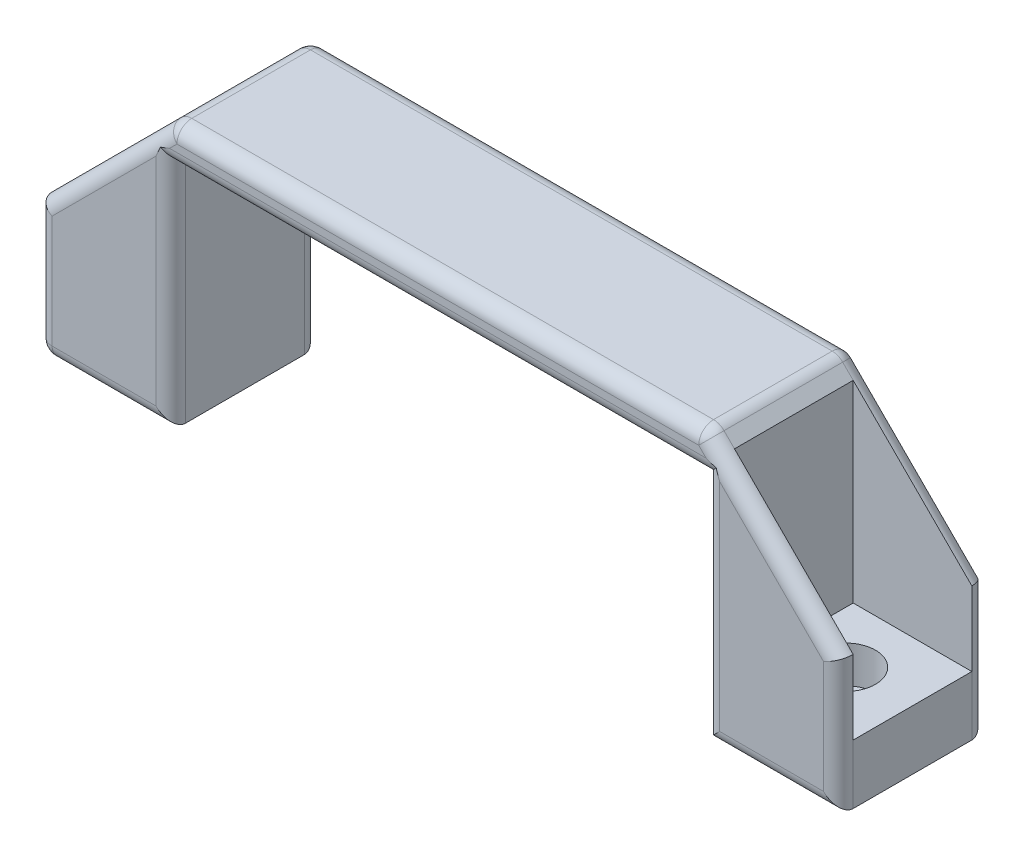
SolidWorks part; units mm, degrees
ref_plane "前视基准面" through (0, 0, 0) normal (0, 0, 1) x (1, 0, 0)
ref_plane "上视基准面" through (0, 0, 0) normal (0, 1, 0) x (1, 0, 0)
ref_plane "右视基准面" through (0, 0, 0) normal (1, 0, 0) x (0, 0, -1)
other "Configuration Table"
sketch "草图1" plane through (0, 0, 0) normal (0, 0, 1) x (1, 0, 0)
  line L0 (-54, 0) -> (-54, 18)
  line L1 (-36, 36) -> (-54, 18)
  line L2 (-36, 0) -> (-36, 31)
  line L3 (-36, 36) -> (36, 36)
  line L4 (-54, 0) -> (-36, 0)
  line L5 (54, 0) -> (36, 0)
  line L6 (-36, 31) -> (36, 31)
  line L7 (0, 31) -> (0, 0) construction
  line L8 (36, 0) -> (36, 31)
  line L9 (36, 36) -> (54, 18)
  line L10 (54, 0) -> (54, 18)
  point P2 (-37.8136, 30)
  point P3 (-54, 18.7225)
  point P8 (-41.4613, 36)
  point P16 (0, 36)
  dimension "D1" = 31
  dimension "D2" = 5
  dimension "D3" = 18
  dimension "D4" = 108
  dimension "D5" = 18
  dimension "D6" = 135
extrude "凸台-拉伸1" add sketch "草图1" along normal mid plane 20
sketch "草图2" plane through (0, 0, 0) normal (0, 1, 0) x (1, 0, 0)
  line L0 (0, 0) -> (0, 23.9133) construction
  circle A0 centre (-45, 0) radius 2.15
  circle A1 centre (45, 0) radius 2.15
  point P7 (0, 0)
  dimension "D1" = 90
  dimension "D2" = 4.3
extrude "切除-拉伸1" cut sketch "草图2" along normal through all
sketch "草图3" plane through (0, 0, 0) normal (0, -1, 0) x (1, 0, 0)
  line L4 (-54, 10) -> (-54, -10) construction
  line L5 (-54, 8) -> (-54, -8)
  line L6 (0, 0) -> (0, 32.7888) construction
  line L7 (38, 8) -> (54, 8)
  line L8 (-38, -8) -> (-38, 8)
  line L9 (-52, -8) -> (-38, -8)
  line L10 (-52, 8) -> (-52, -8)
  line L11 (-38, 8) -> (-52, 8)
  line L12 (-38, -8) -> (-38, 8)
  line L13 (-54, -8) -> (-38, -8)
  line L15 (-38, 8) -> (-54, 8)
  line L16 (54, -8) -> (38, -8)
  line L17 (38, -8) -> (38, 8)
  line L18 (54, 8) -> (54, -8)
  dimension "D1" = 2
extrude "切除-拉伸2" cut sketch "草图3" against normal through all from offset 8 offset against normal yes
sketch "草图4" plane through (0, 8, 0) normal (0, 1, 0) x (1, 0, 0)
  circle A0 centre (45, 0) radius 4
  circle A1 centre (-45, 0) radius 4
  dimension "D1" = 8
  dimension "D2" = 8
extrude "切除-拉伸3" cut sketch "草图4" against normal blind 5
fillet "圆角1" radius 2 23 edges at (-54, 9, 10) (-45, 27, 10) (45, 27, 10) (54, 9, 10) (45, 0, 10) (36, 15.5, 10) (0, 31, 10) (-36, 15.5, 10) (-45, 0, 10) (-36, 15.5, -10) (0, 31, -10) (36, 15.5, -10) (45, 0, -10) (54, 9, -10) (45, 27, -10) (-45, 27, -10) (-54, 9, -10) (-45, 0, -10) (36, 36, 0) (0, 36, 10) (-36, 36, 0) (0, 36, -10) (-54, 0, 0)
